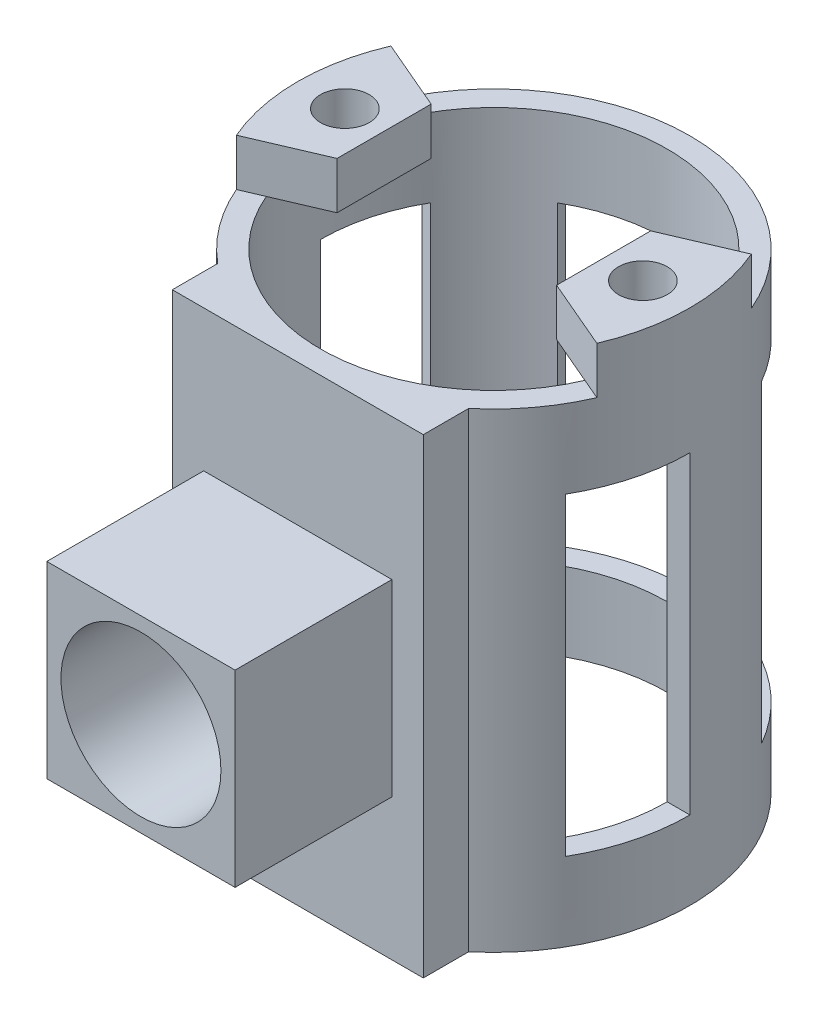
SolidWorks part; units mm, degrees
ref_plane "前视基准面" through (0, 0, 0) normal (0, 0, 1) x (1, 0, 0)
ref_plane "上视基准面" through (0, 0, 0) normal (0, 1, 0) x (1, 0, 0)
ref_plane "右视基准面" through (0, 0, 0) normal (1, 0, 0) x (0, 0, -1)
other "Configuration Table"
sketch "草图1" plane through (0, 0, 0) normal (0, 1, 0) x (1, 0, 0)
  circle A0 centre (0, 0) radius 11.05
  circle A1 centre (0, 0) radius 12.5
  dimension "D1" = 22.1
  dimension "D2" = 25
extrude "凸台-拉伸1" add sketch "草图1" along normal blind 5
sketch "草图2" plane through (0, 5, 0) normal (0, 1, 0) x (1, 0, 0)
  line L0 (0, 0) -> (0, 12.5)
  line L1 (0, 0) -> (6.25, 10.8253)
  line L2 (0, 0) -> (10.8253, 6.25)
  line L3 (0, 0) -> (12.5, 0)
  line L4 (0, 0) -> (10.8253, -6.25)
  line L5 (0, 0) -> (6.25, -10.8253)
  line L6 (0, 0) -> (0, -12.5)
  line L7 (0, 0) -> (-6.25, -10.8253)
  line L8 (0, 0) -> (-10.8253, -6.25)
  line L9 (0, 0) -> (-12.5, 0)
  line L10 (0, 0) -> (-10.8253, 6.25)
  line L11 (0, 0) -> (-6.25, 10.8253)
  circle A0 centre (0, 0) radius 12.5 construction
  point P19 (0, 0)
  circle M1 centre (0, 0) radius 12.5
  circle M2 centre (0, 0) radius 11.05
  dimension "D1" = 12
extrude "凸台-拉伸2" add sketch "草图2" along normal blind 20 contours L11 L10 M2 M1 | L1 L0 M2 M1 | L3 L2 M2 M1 | L5 L4 M2 M1 | L7 L6 M2 M1 | L9 L8 M2 M1 region at (3.0167, 5, -11.2585) region at (11.2585, 5, -3.0167) region at (8.2418, 5, 8.2418) region at (-3.0167, 5, 11.2585) region at (-11.2585, 5, 3.0167) region at (-8.2418, 5, -8.2418)
sketch "草图3" plane through (0, 25, 0) normal (0, 1, 0) x (1, 0, 0)
  circle A0 centre (0, 0) radius 12.5
  circle A1 centre (0, 0) radius 11.05
  arc A2 (-10.8253, 6.25) -> (-12.5, 0) centre (0, 0) ccw construction
  arc A3 (-9.5696, 5.525) -> (-11.05, 0) centre (0, 0) ccw construction
extrude "凸台-拉伸3" add sketch "草图3" along normal blind 5
sketch "草图4" plane through (0, 30, 0) normal (0, 1, 0) x (1, 0, 0)
  line L0 (0, 0) -> (0, 3.3292) construction
  line L1 (-9.5, 0) -> (9.5, 0) construction
  line L4 (-7, 3) -> (-7, -3)
  line L8 (7, 3) -> (7, -3)
  line L10 (0, 0) -> (-11.4893, 4.924)
  line L11 (0, 0) -> (-11.4893, -4.924)
  line L12 (0, 0) -> (11.4893, 4.924)
  line L13 (0, 0) -> (11.4893, -4.924)
  circle A0 centre (-9.5, 0) radius 1.55
  circle A1 centre (9.5, 0) radius 1.55
  circle A2 centre (0, 0) radius 12.5
  circle A3 centre (0, 0) radius 11.05
  circle A4 centre (0, 0) radius 12.5 construction
  circle A5 centre (0, 0) radius 11.05 construction
  circle A6 centre (0, 0) radius 6
  circle M7 centre (0, 0) radius 12.5
  circle M8 centre (0, 0) radius 11.05
  dimension "D1" = 3.1
  dimension "D3" = 12
  dimension "D2" = 19
  dimension "D4" = 3
  dimension "D5" = 6
  dimension "D6" = 7
extrude "凸台-拉伸5" add sketch "草图4" along normal blind 3 contours A0 L4 M8 | M8 M7 | A1 L8 M8 | M8 M7 region at (-7.096, 30, 0) region at (-11.4704, 30, 0) region at (10.7303, 30, -2.2025) region at (11.4704, 30, 0)
sketch "草图6" plane through (0, 30, 0) normal (0, 1, 0) x (1, 0, 0)
  line L0 (-7.072, -8.4905) -> (-8, -9.6047)
  line L1 (0, 0) -> (0, -2.665) construction
  line L2 (7.072, -8.4905) -> (8, -9.6047)
  line L3 (8, -12.5) -> (-8, -12.5)
  line L4 (-8, -12.5) -> (-8, -9.6047)
  line L5 (8, -12.5) -> (8, -9.6047)
  line L6 (-8, -9.6047) -> (-7.072, -8.4905)
  line L7 (7.072, -8.4905) -> (8, -9.6047)
  circle A1 centre (0, 0) radius 12.5
  arc A3 (-11.4893, -4.924) -> (11.4893, -4.924) centre (0, 0) ccw construction
  circle A4 centre (0, 0) radius 11.05
  arc A5 (-10.1566, -4.3528) -> (10.1566, -4.3528) centre (0, 0) ccw construction
  point P6 (-6.359, -8.2872)
  point P17 (0, -12.5)
  point P20 (0, 0)
  point P21 (0, 0)
  point P22 (0, 0)
  dimension "D1" = 16
extrude "凸台-拉伸7" add sketch "草图6" against normal up to surface (30 mm away) contours L4 L3 L0 | L1 A4 L0 | L3 L5 L0 | L1 L0 L2 region at (0, 30, 11.2149) region at (-6.0493, 30, 11.6519) region at (6.0493, 30, 11.6519) up to face at (0, 0, 12.5)
sketch "草图7" plane through (0, 0, 12.5) normal (0, 0, 1) x (1, 0, 0)
  line L0 (-6, 21) -> (-6, 9)
  line L1 (-6, 9) -> (6, 9)
  line L2 (6, 9) -> (6, 21)
  line L3 (6, 21) -> (-6, 21)
  line L6 (8, 0) -> (8, 30) construction
  line L7 (8, 30) -> (-8, 30) construction
  line L8 (0, 21) -> (0, 9) construction
  line L10 (-6, 15) -> (6, 15) construction
  circle A0 centre (0, 15) radius 5.1
  dimension "D5" = 10.2
  dimension "D1" = 12
  dimension "D2" = 12
  dimension "D3" = 2
  dimension "D4" = 9
extrude "凸台-拉伸8" add sketch "草图7" along normal blind 10 contours L3 L0 L1 L2 | A0
